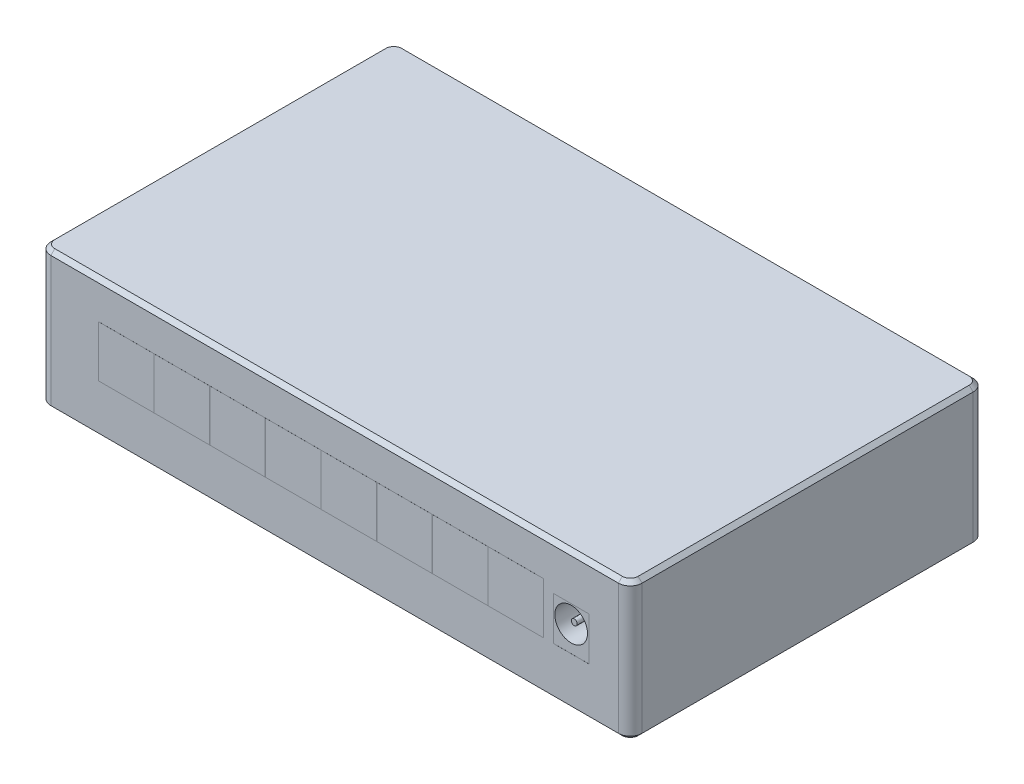
SolidWorks part; units mm, degrees
ref_plane "前视基准面" through (0, 0, 0) normal (0, 0, 1) x (1, 0, 0)
ref_plane "上视基准面" through (0, 0, 0) normal (0, 1, 0) x (1, 0, 0)
ref_plane "右视基准面" through (0, 0, 0) normal (1, 0, 0) x (0, 0, -1)
other "Configuration Table"
sketch "草图1" plane through (0, 0, 0) normal (0, 1, 0) x (1, 0, 0)
  line L0 (41.7512, 0) -> (191.7512, 0)
  line L1 (191.7512, 0) -> (191.7512, 90)
  line L2 (191.7512, 90) -> (41.7512, 90)
  line L3 (41.7512, 90) -> (41.7512, 0)
extrude "凸台-拉伸1" add sketch "草图1" along normal blind 35
sketch "草图2" plane through (0, 0, 0) normal (0, -1, 0) x (1, 0, 0)
  circle A0 centre (173.7512, -18) radius 5
  circle A1 centre (59.7512, -18) radius 5
  circle A2 centre (59.7512, -72) radius 5
  circle A3 centre (173.7512, -72) radius 5
extrude "凸台-拉伸2" add sketch "草图2" along normal blind 1.8
fillet "圆角1" radius 3 4 edges at (191.7512, 17.5, 0) (191.7512, 17.5, -90) (41.7512, 17.5, 0) (41.7512, 17.5, -90)
chamfer "倒角1" distance 1 angle 45 16 edges at (116.7512, 35, 0) (190.8726, 35, -0.8787) (42.6299, 35, -0.8787) (191.7512, 35, -45) (41.7512, 35, -45) (190.8726, 35, -89.1213) (42.6299, 35, -89.1213) (116.7512, 35, -90) (116.7512, 0, 0) (190.8726, 0, -0.8787) (42.6299, 0, -0.8787) (191.7512, 0, -45) (41.7512, 0, -45) (190.8726, 0, -89.1213) (42.6299, 0, -89.1213) (116.7512, 0, -90)
chamfer "倒角2" distance 1.8 angle 45 4 edges at (59.7512, -1.8, -77) (59.7512, -1.8, -23) (173.7512, -1.8, -77) (173.7512, -1.8, -23)
sketch "草图3" plane through (0, 0, 0) normal (0, 0, 1) x (1, 0, 0)
  circle A0 centre (176.7512, 19) radius 4.15
extrude "切除-拉伸1" cut sketch "草图3" against normal blind 5.8
sketch "草图4" plane through (0, 0, -5.8) normal (0, 0, 1) x (1, 0, 0)
  circle A0 centre (176.7512, 19) radius 0.75
extrude "凸台-拉伸3" add sketch "草图4" along normal blind 5
sketch "草图5" plane through (0, 0, 0) normal (0, 0, 1) x (1, 0, 0)
  line L1 (176.7512, 23.5) -> (172.2512, 23.5)
  line L2 (172.2512, 23.5) -> (172.2512, 12.5)
  line L3 (172.2512, 12.5) -> (181.2512, 12.5)
  line L4 (181.2512, 12.5) -> (181.2512, 23.5)
  line L5 (181.2512, 23.5) -> (176.7512, 23.5)
extrude "切除-拉伸2" cut sketch "草图5" against normal blind 0.01
sketch "草图6" plane through (0, 0, 0) normal (0, 0, 1) x (1, 0, 0)
  line L0 (155.7262, 12.5) -> (155.7262, 25.5)
  line L2 (141.6012, 12.5) -> (141.6012, 25.5)
  line L3 (169.7512, 12.5) -> (155.7262, 12.5)
  line L5 (155.7262, 25.5) -> (169.7512, 25.5)
  line L6 (169.7512, 25.5) -> (169.7512, 12.5)
  line L7 (155.6262, 12.5) -> (141.6012, 12.5)
  line L8 (141.6012, 25.5) -> (155.6262, 25.5)
  line L9 (155.6262, 25.5) -> (155.6262, 12.5)
  line L10 (127.4762, 12.5) -> (127.4762, 25.5)
  line L11 (141.5012, 12.5) -> (127.4762, 12.5)
  line L12 (127.4762, 25.5) -> (141.5012, 25.5)
  line L13 (141.5012, 25.5) -> (141.5012, 12.5)
  line L14 (113.3512, 12.5) -> (113.3512, 25.5)
  line L15 (127.3762, 12.5) -> (113.3512, 12.5)
  line L16 (113.3512, 25.5) -> (127.3762, 25.5)
  line L17 (127.3762, 25.5) -> (127.3762, 12.5)
  line L18 (99.2262, 12.5) -> (99.2262, 25.5)
  line L19 (113.2512, 12.5) -> (99.2262, 12.5)
  line L20 (99.2262, 25.5) -> (113.2512, 25.5)
  line L21 (113.2512, 25.5) -> (113.2512, 12.5)
  line L22 (85.1012, 12.5) -> (85.1012, 25.5)
  line L23 (99.1262, 12.5) -> (85.1012, 12.5)
  line L24 (85.1012, 25.5) -> (99.1262, 25.5)
  line L25 (99.1262, 25.5) -> (99.1262, 12.5)
  line L26 (70.9762, 12.5) -> (70.9762, 25.5)
  line L27 (85.0012, 12.5) -> (70.9762, 12.5)
  line L28 (70.9762, 25.5) -> (85.0012, 25.5)
  line L29 (85.0012, 25.5) -> (85.0012, 12.5)
  line L30 (56.8512, 12.5) -> (56.8512, 25.5)
  line L31 (70.8762, 12.5) -> (56.8512, 12.5)
  line L32 (56.8512, 25.5) -> (70.8762, 25.5)
  line L33 (70.8762, 25.5) -> (70.8762, 12.5)
  line L34 (155.7262, 12.5) -> (141.6012, 12.5) construction
  dimension "D1" = 8
  dimension "D2" = 14.125
extrude "凸台-拉伸4" add sketch "草图6" along normal blind 0.01
